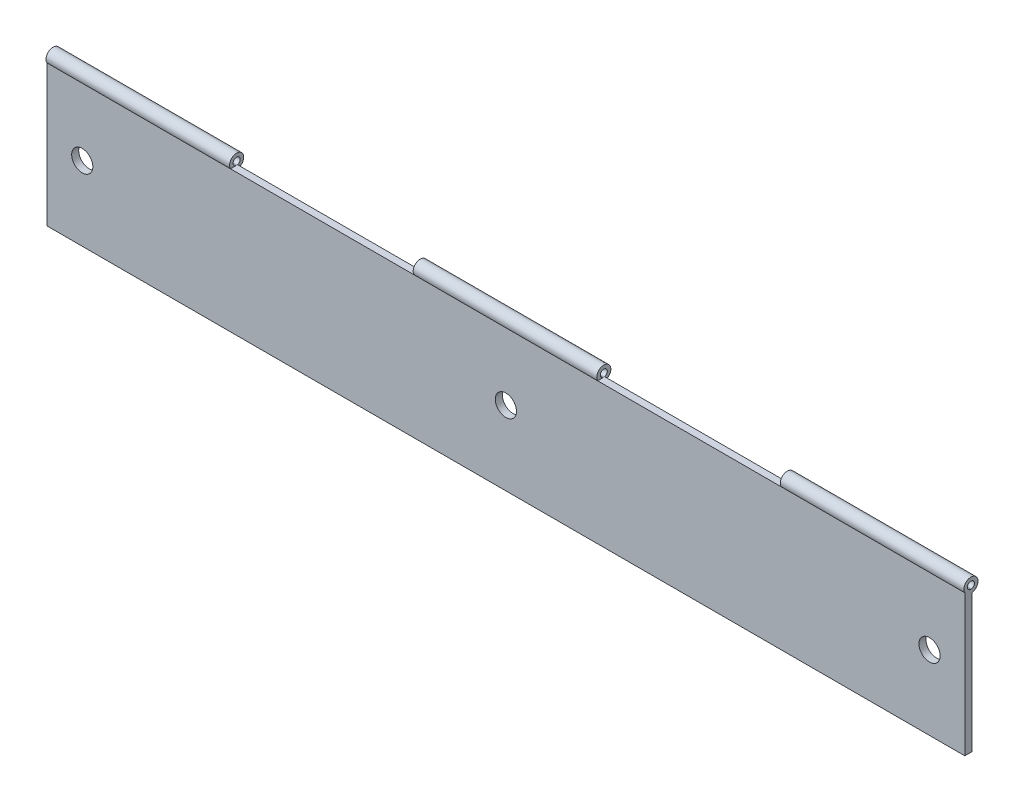
SolidWorks part; units mm, degrees
ref_plane "Front Plane" through (0, 0, 0) normal (0, 0, 1) x (1, 0, 0)
ref_plane "Top Plane" through (0, 0, 0) normal (0, 1, 0) x (1, 0, 0)
ref_plane "Right Plane" through (0, 0, 0) normal (1, 0, 0) x (0, 0, -1)
sketch "Sketch1" plane through (0, 0, 0) normal (0, 0, 1) x (1, 0, 0)
  line L1 (0, 0) -> (130, 0)
  line L2 (0, 0) -> (0, 20)
  line L3 (0, 20) -> (130, 20)
  line L4 (130, 0) -> (130, 20)
  circle A0 centre (65, 10.5) radius 1.5
  circle A1 centre (5, 10.5) radius 1.5
  circle A2 centre (125, 10.5) radius 1.5
  dimension "D3" = 3
  dimension "D4" = 3
  dimension "D5" = 3
  dimension "D1" = 130
  dimension "D2" = 20
  dimension "D6" = 60
  dimension "D7" = 60
  dimension "D8" = 65
  dimension "D9" = 9.5
extrude "Boss-Extrude1" add sketch "Sketch1" along normal blind 1
sketch "Sketch3" plane through (0, 0, 0) normal (1, 0, 0) x (0, 0, -1)
  circle A0 centre (-0.1316, 20.4958) radius 1
  circle A1 centre (-0.1316, 20.4958) radius 0.5
  dimension "D1" = 2
  dimension "D2" = 1
extrude "Boss-Extrude3" add sketch "Sketch3" along normal blind 26
sketch "Sketch4" plane through (0, 0, 0) normal (0, 0, 1) x (1, 0, 0)
  line L0 (130.8448, 20.5139) -> (-2.3082, 20.5139)
pattern_linear "LPattern1" count 3 spacing 52 along (1, 0, 0) of "Boss-Extrude3"
